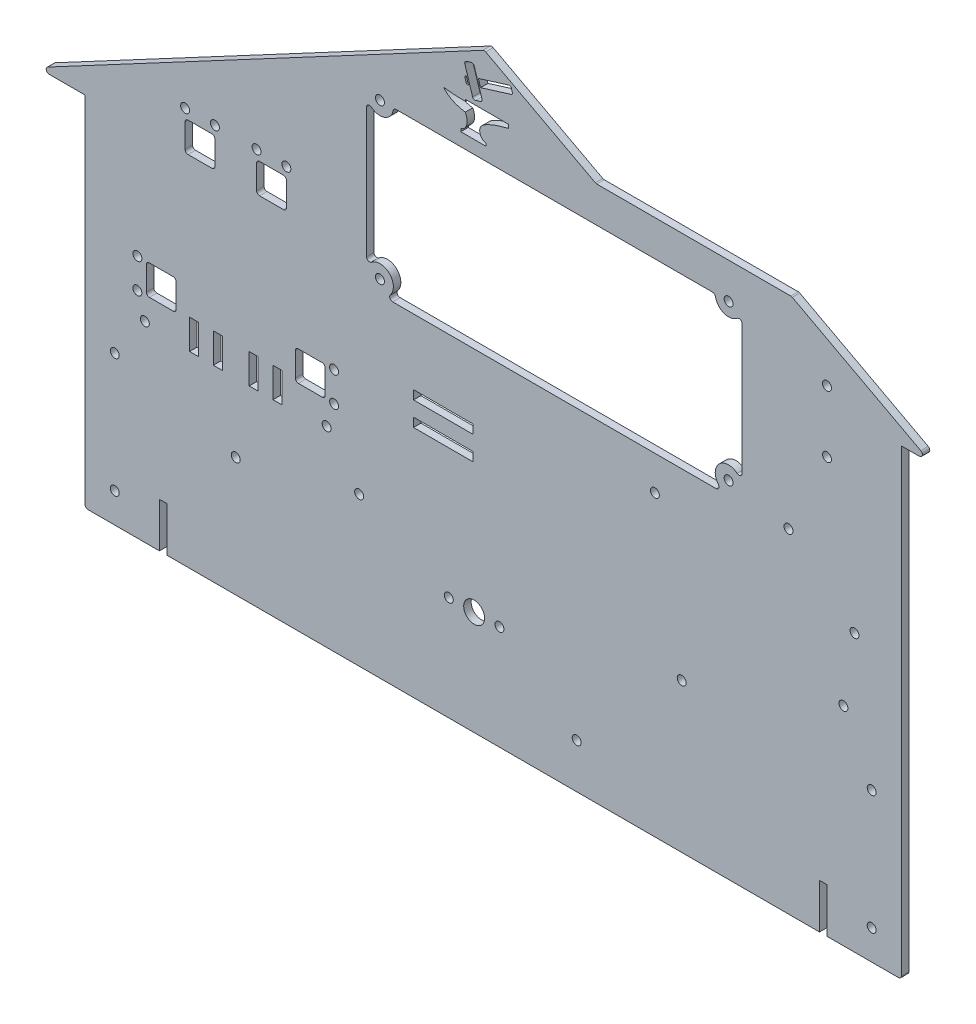
SolidWorks part; units mm, degrees
ref_plane "前视基准面" through (0, 0, 0) normal (0, 0, 1) x (1, 0, 0)
ref_plane "上视基准面" through (0, 0, 0) normal (0, 1, 0) x (1, 0, 0)
ref_plane "右视基准面" through (0, 0, 0) normal (1, 0, 0) x (0, 0, -1)
sketch "草图1" plane through (0, 0, 0) normal (0, 0, 1) x (1, 0, 0)
  line L0 (-63.75, 0) -> (0, 0) construction
  line L1 (-280, 150) -> (20, 150)
  line L2 (-280, 150) -> (-280, -50)
  line L3 (-280, -50) -> (20, -50)
  line L4 (20, 150) -> (20, -50)
  line L5 (-63.75, 0) -> (-9.4828, 19.7517) construction
  circle A0 centre (-9.4828, 19.7517) radius 1.5
  circle A1 centre (-27.9161, 61.985) radius 1.5
  circle A2 centre (-5.7494, 42.7517) radius 1.5
  point P0 (0, 0)
  point P12 (-63.75, 0)
  dimension "D3" = 3
  dimension "D4" = 42.2333
  dimension "D5" = 18.4333
  dimension "D6" = 22.1667
  dimension "D7" = 23
  dimension "D8" = 63.75
  dimension "D13" = 3
  dimension "D1" = 300
  dimension "D2" = 200
  dimension "D9" = 57.75
  dimension "D10" = 20
  dimension "D11" = 50
  dimension "D12" = 20
extrude "凸台-拉伸1" add sketch "草图1" along normal blind 2.5
sketch "草图2" plane through (0, 0, 2.5) normal (0, 0, 1) x (1, 0, 0)
  line L1 (-280, -50) -> (20, -50) construction
  circle A0 centre (-63.75, 0) radius 1.5
  circle A1 centre (-9.4828, 19.7517) radius 1.5 construction
  dimension "D1" = 63.75
  dimension "D2" = 50
extrude "切除-拉伸1" cut sketch "草图2" against normal through all
sketch "草图3" plane through (0, 0, 2.5) normal (0, 0, 1) x (1, 0, 0)
  line L0 (-280, -50) -> (20, -50) construction
  circle A0 centre (-133.4032, -15) radius 3.5
  circle A1 centre (-63.75, 0) radius 1.5 construction
  circle A2 centre (-213.4032, -10) radius 1.5
  dimension "D1" = 7
  dimension "D2" = 71.25
  dimension "D3" = 35
  dimension "D4" = 5
  dimension "D5" = 80
  dimension "D6" = 3
extrude "切除-拉伸2" cut sketch "草图3" against normal through all
sketch "草图4" plane through (0, 0, 2.5) normal (0, 0, 1) x (1, 0, 0)
  line L0 (-213.4032, 93.9226) -> (-213.4032, -10) construction
  line L1 (-223.4032, 111.2388) -> (-223.4032, 26.2684) construction
  line L2 (-203.4032, 111.2388) -> (-203.4032, 26.2684) construction
  line L4 (-225.9032, 13) -> (-220.9032, 13) construction
  line L5 (-225.9032, 13) -> (-225.9032, 53) construction
  line L6 (-225.9032, 53) -> (-220.9032, 53) construction
  line L7 (-220.9032, 13) -> (-220.9032, 53) construction
  line L8 (-225.9032, 13) -> (-220.9032, 53) construction
  line L9 (-225.9032, 53) -> (-220.9032, 13) construction
  line L13 (-220.9032, 13) -> (-217.9032, 13)
  line L14 (-225.9032, 23) -> (-228.9032, 23)
  line L15 (-225.9032, 23) -> (-225.9032, 13)
  line L16 (-225.9032, 13) -> (-228.9032, 13)
  line L17 (-228.9032, 23) -> (-228.9032, 13)
  line L18 (-217.9032, 23) -> (-217.9032, 13)
  line L19 (-220.9032, 23) -> (-217.9032, 23)
  line L20 (-220.9032, 23) -> (-220.9032, 13)
  line L21 (-205.9032, 23) -> (-205.9032, 13)
  line L22 (-205.9032, 23) -> (-208.9032, 23)
  line L23 (-208.9032, 23) -> (-208.9032, 13)
  line L24 (-205.9032, 13) -> (-208.9032, 13)
  line L25 (-200.9032, 13) -> (-197.9032, 13)
  line L26 (-197.9032, 23) -> (-197.9032, 13)
  line L27 (-200.9032, 23) -> (-197.9032, 23)
  line L28 (-200.9032, 23) -> (-200.9032, 13)
  circle A2 centre (-213.4032, -10) radius 1.5 construction
  point P4 (-213.4032, -10)
  point P12 (-223.4032, 33)
  dimension "D5" = 23
  dimension "D1" = 10
  dimension "D2" = 5
  dimension "D3" = 40
  dimension "D4" = 3
  dimension "D6" = 10
extrude "切除-拉伸3" cut sketch "草图4" against normal through all
sketch "草图5" plane through (0, 0, 2.5) normal (0, 0, 1) x (1, 0, 0)
  line L0 (-153.75, 30) -> (-133.75, 30) construction
  line L1 (-143.75, 31.5) -> (-143.75, 28.5) construction
  line L2 (-175.7832, 34) -> (-111.0917, 34) construction
  line L3 (-153.75, 31.5) -> (-133.75, 31.5)
  line L4 (-153.75, 31.5) -> (-153.75, 28.5)
  line L5 (-153.75, 28.5) -> (-133.75, 28.5)
  line L6 (-133.75, 31.5) -> (-133.75, 28.5)
  line L7 (-153.75, 39.5) -> (-133.75, 39.5)
  line L8 (-133.75, 36.5) -> (-133.75, 39.5)
  line L9 (-153.75, 36.5) -> (-133.75, 36.5)
  line L10 (-153.75, 36.5) -> (-153.75, 39.5)
  circle A0 centre (-72.75, 50) radius 1.5
  circle A1 centre (-63.75, 0) radius 1.5 construction
  dimension "D1" = 50
  dimension "D2" = 9
  dimension "D3" = 3
  dimension "D5" = 30
  dimension "D4" = 80
  dimension "D6" = 3
  dimension "D7" = 20
  dimension "D8" = 5
extrude "切除-拉伸4" cut sketch "草图5" against normal through all
sketch "草图6" plane through (0, 0, 2.5) normal (0, 0, 1) x (1, 0, 0)
  line L0 (-130, 150) -> (-130, -50) construction
  line L1 (20, 150) -> (-280, 150) construction
  line L2 (-280, -50) -> (20, -50) construction
  line L3 (-280, 70) -> (-130, 150)
  line L4 (-280, 150) -> (-280, -50) construction
  line L5 (-130, 150) -> (-92.5, 130)
  line L6 (-92.5, 130) -> (20, 130)
  line L7 (20, -50) -> (20, 150) construction
  line L8 (-280, 70) -> (-264, 70)
  line L9 (-264, 70) -> (-264, -50)
  line L10 (-264, -50) -> (-280, -50)
  line L11 (-280, -50) -> (-280, 70)
  line L12 (-280, 150) -> (-280, 70)
  line L13 (-280, 150) -> (-130, 150)
  line L14 (-130, 150) -> (20, 150)
  line L15 (20, 150) -> (20, 130)
  line M38 (20, -50) -> (20, 150)
  line M39 (20, 150) -> (-280, 150)
  line M40 (-280, 150) -> (-280, -50)
  line M41 (-280, -50) -> (20, -50)
  dimension "D1" = 20
  dimension "D2" = 120
  dimension "D3" = 16
extrude "切除-拉伸5" cut sketch "草图6" against normal through all contours L3 M40 M39 | L9 L8 M40 M41 | L5 L6 M38 M39 region at (-230, 123.3333, 2.5) region at (-272, 10, 2.5) region at (-46.0714, 140.4762, 2.5)
sketch "草图7" plane through (0, 0, 2.5) normal (0, 0, 1) x (1, 0, 0)
  line L0 (-133.4032, -15) -> (-133.4032, -6.7332) construction
  line L1 (-133.4032, -15) -> (-141.9032, -15) construction
  circle A0 centre (-141.9032, -15) radius 1.5
  circle A1 centre (-124.9032, -15) radius 1.5
  dimension "D1" = 3
  dimension "D2" = 17
extrude "切除-拉伸6" cut sketch "草图7" against normal through all
sketch "草图8" plane through (0, 0, 2.5) normal (0, 0, 1) x (1, 0, 0)
  circle A0 centre (-254, 0) radius 1.5
  circle A1 centre (-254, -40) radius 1.5
  circle A2 centre (-172, 0) radius 1.5
  circle A3 centre (-99, -35) radius 1.5
  circle A4 centre (0, -40) radius 1.5
  circle A5 centre (0, 0) radius 1.5
extrude "切除-拉伸7" cut sketch "草图8" against normal through all
sketch "草图10" plane through (0, 0, 2.5) normal (0, 0, 1) x (1, 0, 0)
  line L0 (-15, 89.3) -> (-15, 110) construction
  line L1 (20, -50) -> (20, 130) construction
  line L2 (-92.5, 130) -> (20, 130) construction
  circle A0 centre (-15, 110) radius 1.5
  circle A1 centre (-15, 89.3) radius 1.5
  dimension "D1" = 20.7
  dimension "D2" = 3
  dimension "D3" = 35
  dimension "D4" = 20
extrude "切除-拉伸9" cut sketch "草图10" against normal through all
sketch "草图11" plane through (0, 0, 2.5) normal (0, 0, 1) x (1, 0, 0)
  line L0 (-213.4032, -10) -> (-213.4032, 45.586) construction
  line L1 (-264, -50) -> (20, -50) construction
  line L38 (-201.4032, 70) -> (-201.4032, 83) construction
  line L39 (-180.4032, 32) -> (-180.4032, 22) construction
  line L40 (-180.4032, 27) -> (-193.4032, 27) construction
  line L41 (-197.9032, 23) -> (-200.9032, 23) construction
  line L42 (-192.4032, 32) -> (-184.4032, 32)
  line L43 (-193.4032, 31) -> (-193.4032, 23)
  line L44 (-192.4032, 22) -> (-184.4032, 22)
  line L45 (-183.4032, 31) -> (-183.4032, 23)
  line L46 (-193.4032, 32) -> (-183.4032, 22) construction
  line L47 (-193.4032, 22) -> (-183.4032, 32) construction
  line L52 (-206.4032, 83) -> (-196.4032, 83) construction
  line L53 (-205.4032, 80) -> (-197.4032, 80)
  line L54 (-206.4032, 79) -> (-206.4032, 71)
  line L55 (-205.4032, 70) -> (-197.4032, 70)
  line L56 (-196.4032, 79) -> (-196.4032, 71)
  line L57 (-206.4032, 80) -> (-196.4032, 70) construction
  line L58 (-206.4032, 70) -> (-196.4032, 80) construction
  line L59 (-234.4032, 22) -> (-242.4032, 22)
  line L60 (-243.4032, 31) -> (-243.4032, 23)
  line L61 (-234.4032, 32) -> (-242.4032, 32)
  line L62 (-233.4032, 31) -> (-233.4032, 23)
  line L63 (-220.4032, 79) -> (-220.4032, 71)
  line L64 (-221.4032, 70) -> (-229.4032, 70)
  line L65 (-230.4032, 79) -> (-230.4032, 71)
  line L66 (-221.4032, 80) -> (-229.4032, 80)
  circle A0 centre (-243.9032, 14.3) radius 1.5
  circle A1 centre (-182.9032, 14.3) radius 1.5
  circle A18 centre (-180.4032, 32) radius 1.5
  circle A19 centre (-180.4032, 22) radius 1.5
  arc A20 (-184.4032, 32) -> (-183.4032, 31) centre (-184.4032, 31) cw
  arc A21 (-184.4032, 22) -> (-183.4032, 23) centre (-184.4032, 23) ccw
  arc A22 (-193.4032, 23) -> (-192.4032, 22) centre (-192.4032, 23) ccw
  arc A23 (-192.4032, 32) -> (-193.4032, 31) centre (-192.4032, 31) ccw
  arc A26 (-197.4032, 80) -> (-196.4032, 79) centre (-197.4032, 79) cw
  arc A27 (-197.4032, 70) -> (-196.4032, 71) centre (-197.4032, 71) ccw
  arc A28 (-206.4032, 71) -> (-205.4032, 70) centre (-205.4032, 71) ccw
  arc A29 (-205.4032, 80) -> (-206.4032, 79) centre (-205.4032, 79) ccw
  circle A30 centre (-206.4032, 83) radius 1.5
  circle A31 centre (-196.4032, 83) radius 1.5
  circle A32 centre (-246.4032, 22) radius 1.5
  circle A33 centre (-246.4032, 32) radius 1.5
  arc A34 (-242.4032, 22) -> (-243.4032, 23) centre (-242.4032, 23) cw
  arc A35 (-242.4032, 32) -> (-243.4032, 31) centre (-242.4032, 31) ccw
  arc A36 (-233.4032, 23) -> (-234.4032, 22) centre (-234.4032, 23) cw
  arc A37 (-234.4032, 32) -> (-233.4032, 31) centre (-234.4032, 31) cw
  circle A38 centre (-230.4032, 83) radius 1.5
  circle A39 centre (-220.4032, 83) radius 1.5
  arc A40 (-221.4032, 80) -> (-220.4032, 79) centre (-221.4032, 79) cw
  arc A41 (-220.4032, 71) -> (-221.4032, 70) centre (-221.4032, 71) cw
  arc A42 (-229.4032, 70) -> (-230.4032, 71) centre (-229.4032, 71) cw
  arc A43 (-229.4032, 80) -> (-230.4032, 79) centre (-229.4032, 79) ccw
  point P15 (-188.4032, 27)
  point P21 (-188.4032, 27)
  point P39 (-201.4032, 83)
  point P42 (-201.4032, 75)
  point P48 (-201.4032, 75)
  dimension "D1" = 61
  dimension "D2" = 3
  dimension "D6" = 8
  dimension "D8" = 25
  dimension "D10" = 1
  dimension "D11" = 3
  dimension "D4" = 3
  dimension "D5" = 10
  dimension "D13" = 1
  dimension "D14" = 10
  dimension "D3" = 64.3
  dimension "D7" = 10
  dimension "D9" = 4
  dimension "D12" = 10
  dimension "D15" = 52
  dimension "D16" = 12
  dimension "D17" = 8
extrude "切除-拉伸14" cut sketch "草图11" against normal through all
sketch "草图13" plane through (0, 0, 2.5) normal (0, 0, 1) x (1, 0, 0)
  line L0 (-92.5, 130) -> (20, 130) construction
  line L1 (-165, 118) -> (-48, 118) construction
  line L2 (-165, 118) -> (-165, 66) construction
  line L3 (-165, 66) -> (-48, 66) construction
  line L4 (-48, 118) -> (-48, 66) construction
  line L5 (-169, 122) -> (-44, 122) construction
  line L6 (-169, 122) -> (-169, 62) construction
  line L7 (-169, 62) -> (-44, 62) construction
  line L8 (-44, 122) -> (-44, 62) construction
  line L9 (20, -50) -> (20, 130) construction
  circle A2 centre (-165, 118) radius 1.5
  circle A3 centre (-48, 118) radius 1.5
  circle A4 centre (-48, 66) radius 1.5
  circle A5 centre (-165, 66) radius 1.5
  dimension "D1" = 3
  dimension "D8" = 12
  dimension "D9" = 68
  dimension "D2" = 4
  dimension "D3" = 4
  dimension "D4" = 4
  dimension "D5" = 4
  dimension "D6" = 125
  dimension "D7" = 60
extrude "切除-拉伸12" cut sketch "草图13" against normal through all
sketch "草图14" plane through (0, 0, 2.5) normal (0, 0, 1) x (1, 0, 0)
  line L0 (-712.7575, -216.4685) -> (-179.4241, -216.4685) construction
  line L1 (-136.2334, 132.5544) -> (-121.9472, 132.5544)
  line L2 (-121.9472, 132.5544) -> (-121.9472, 131.3357)
  line L3 (-137.8749, 123.2981) -> (-137.8749, 122.3827)
  line L4 (-137.8749, 122.3827) -> (-129.3705, 122.3827)
  line L5 (-129.3705, 122.3827) -> (-129.3705, 123.2981)
  line L6 (-136.2334, 132.5544) -> (-136.2334, 131.96)
  line L7 (-136.5276, 142.774) -> (-133.9184, 134.4987)
  line L8 (-132.9149, 133.9763) -> (-131.2944, 134.4872)
  line L9 (-130.772, 135.4907) -> (-133.3812, 143.7661)
  line L10 (-134.3848, 144.2885) -> (-136.0052, 143.7776)
  line L11 (-133.6778, 133.7357) -> (-126.8634, 133.7357) construction
  line L12 (-135.4705, 137.1877) -> (-135.2925, 137.243)
  line L13 (-120.5412, 142.3485) -> (-120.9653, 143.7139)
  line L14 (-121.5911, 144.0431) -> (-131.9789, 140.8166)
  line L15 (-136.5204, 138.8824) -> (-136.0963, 137.5169)
  line L16 (-136.0132, 139.5635) -> (-135.2925, 137.243)
  line L17 (-131.9789, 140.8166) -> (-131.2581, 138.4961)
  line L18 (-136.0132, 139.5635) -> (-136.1912, 139.5082)
  line L20 (-131.2581, 138.4961) -> (-120.8704, 141.7227)
  arc A0 (-133.9184, 134.4987) -> (-132.9149, 133.9763) centre (-133.1554, 134.7392) ccw
  arc A1 (-131.2944, 134.4872) -> (-130.772, 135.4907) centre (-131.535, 135.2502) ccw
  arc A2 (-133.3812, 143.7661) -> (-134.3848, 144.2885) centre (-134.1442, 143.5255) ccw
  arc A3 (-136.5276, 142.774) -> (-136.0052, 143.7776) centre (-135.7646, 143.0146) cw
  arc A4 (-120.8704, 141.7227) -> (-120.5412, 142.3485) centre (-121.0187, 142.2002) ccw
  arc A5 (-120.9653, 143.7139) -> (-121.5911, 144.0431) centre (-121.4428, 143.5656) ccw
  arc A6 (-136.0963, 137.5169) -> (-135.4705, 137.1877) centre (-135.6188, 137.6652) ccw
  arc A7 (-136.1912, 139.5082) -> (-136.5204, 138.8824) centre (-136.0429, 139.0307) ccw
  spline S0 degree 3 poles (-129.3705, 123.2981) (-130.3816, 123.3331) (-131.6527, 124.6471) (-131.531, 127.3171) (-127.8185, 129.8001) (-124.5959, 130.6229) (-121.9472, 131.3357) knots 0 0 0 0 0.185055 0.315034 0.470626 1 1 1 1
  spline S1 degree 2 poles (-136.2334, 131.96) (-139.936, 131.9254) (-143.607, 132.4202) knots 0 0 0 1 1 1
  spline S2 degree 3 poles (-143.607, 132.4202) (-141.9066, 130.1629) (-139.0314, 129.2845) (-136.3668, 128.8231) knots 0 0 0 0 1 1 1 1
  spline S3 degree 3 poles (-136.3668, 128.8231) (-135.3692, 127.028) (-135.4792, 124.0013) (-137.8749, 123.2981) knots 0 0 0 0 1 1 1 1
  dimension "D2" = 0.8
  dimension "D3" = 0.8
  dimension "D4" = 0.8
  dimension "D5" = 0.8
  dimension "D6" = 0.5
  dimension "D7" = 0.5
  dimension "D8" = 0.5
  dimension "D9" = 0.5
  dimension "D1" = 17.5
extrude "切除-拉伸13" cut sketch "草图14" against normal through all
sketch "草图16" plane through (0, 0, 2.5) normal (0, 0, 1) x (1, 0, 0)
  line L0 (-26.875, 130) -> (20, 105)
  line L1 (-92.5, 130) -> (20, 130) construction
  line L2 (20, -50) -> (20, 130) construction
  line L3 (20, 105) -> (20, 130)
  line L4 (20, 130) -> (-26.875, 130)
  line L5 (-264, -50) -> (20, -50) construction
  line L6 (-130, 150) -> (-92.5, 130) construction
  line L7 (20, 105) -> (10, 105)
  line L8 (20, 105) -> (20, -50)
  line L9 (20, -50) -> (10, -50)
  line L10 (10, 105) -> (10, -50)
  dimension "D1" = 10
  dimension "D2" = 25
extrude "切除-拉伸16" cut sketch "草图16" against normal through all contours L3 L4 L0 | L7 L10 L9 L8 region at (4.375, 121.6667, 2.5) region at (15, 27.5, 2.5)
fillet "圆角1" radius 1 7 edges at (-92.5, 130, 1.25) (-130, 150, 1.25) (-280, 70, 1.25) (-264, -50, 1.25) (-26.875, 130, 1.25) (10, -50, 1.25) (20, 105, 1.25)
sketch "草图15" plane through (0, 0, 2.5) normal (0, 0, 1) x (1, 0, 0)
  line L0 (-165, 118) -> (-165, 66) construction
  line L1 (-165, 66) -> (-48, 66) construction
  line L2 (-48, 66) -> (-48, 118) construction
  line L3 (-48, 118) -> (-165, 118) construction
  line L4 (-106.5, 118) -> (-106.5, 66) construction
  line L5 (-165, 92) -> (-48, 92) construction
  line L6 (-160.5, 118) -> (-52.5, 118)
  line L9 (-43.5, 118) -> (-43.5, 66)
  line L10 (-169.5, 118) -> (-169.5, 66)
  line L11 (-165, 61.5) -> (-48, 61.5)
  arc A0 (-169.5, 118) -> (-160.5, 118) centre (-165, 118) ccw
  arc A1 (-43.5, 118) -> (-52.5, 118) centre (-48, 118) cw
  arc A2 (-43.5, 66) -> (-48, 61.5) centre (-48, 66) ccw
  arc A3 (-169.5, 66) -> (-165, 61.5) centre (-165, 66) cw
  dimension "D1" = 4.5
extrude "切除-拉伸15" cut sketch "草图15" against normal through all
sketch "草图9" plane through (0, 0, 2.5) normal (0, 0, 1) x (1, 0, 0)
  line L0 (-263, -50) -> (9, -50) construction
  line L1 (-239, -50) -> (-236.5, -50)
  line L2 (-239, -50) -> (-239, -35)
  line L3 (-239, -35) -> (-236.5, -35)
  line L4 (-236.5, -50) -> (-236.5, -35)
  line L9 (-264, 70) -> (-264, -49) construction
  line L10 (-127, -50) -> (-127, -19.9681) construction
  line L11 (-15, -35) -> (-17.5, -35)
  line L12 (-17.5, -50) -> (-17.5, -35)
  line L13 (-15, -50) -> (-17.5, -50)
  line L14 (-15, -50) -> (-15, -35)
  dimension "D1" = 15
  dimension "D2" = 2.5
  dimension "D3" = 25
extrude "切除-拉伸8" cut sketch "草图9" against normal through all
fillet "圆角2" radius 1 8 edges at (-52.5, 118, 1.25) (-43.5, 118, 1.25) (-43.5, 66, 1.25) (-48, 61.5, 1.25) (-165, 61.5, 1.25) (-169.5, 66, 1.25) (-169.5, 118, 1.25) (-160.5, 118, 1.25)
